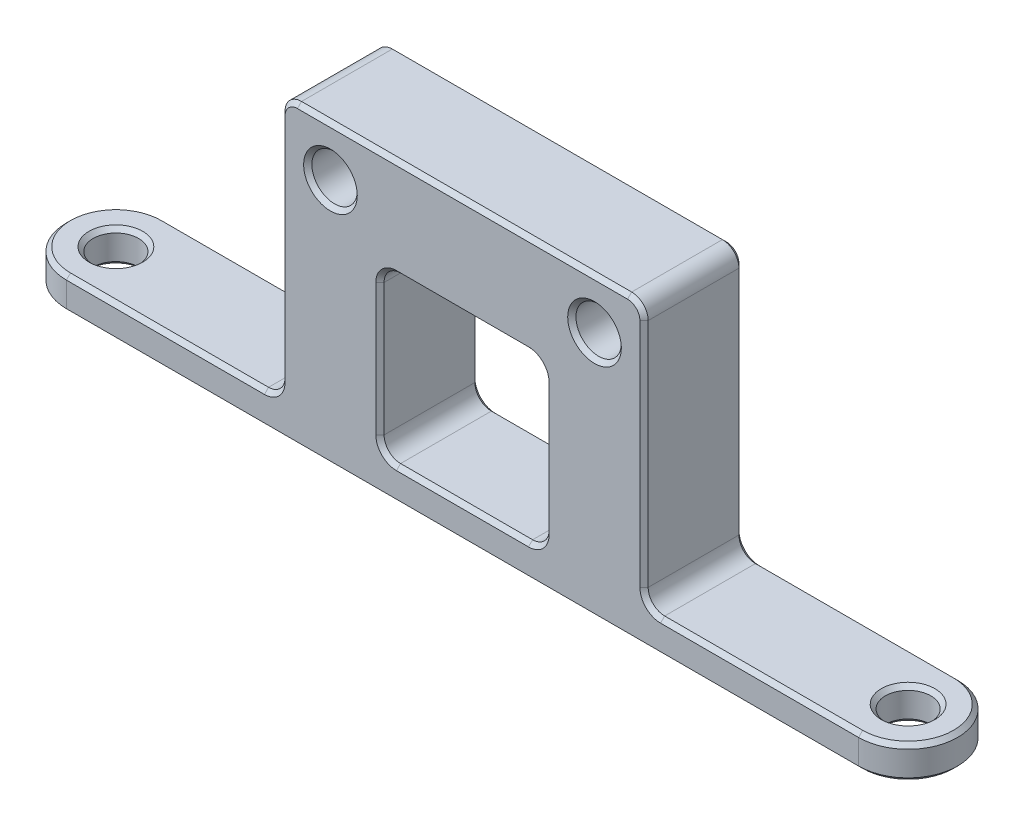
SolidWorks part; units mm, degrees
ref_plane "Front Plane" through (0, 0, 0) normal (0, 0, 1) x (1, 0, 0)
ref_plane "Top Plane" through (0, 0, 0) normal (0, 1, 0) x (1, 0, 0)
ref_plane "Right Plane" through (0, 0, 0) normal (1, 0, 0) x (0, 0, -1)
sketch "Sketch2" plane through (0, 0, 0) normal (0, 1, 0) x (1, 0, 0)
  line L0 (-38.1, 0) -> (38.1, 0) construction
  line L5 (-38.1, 4.7625) -> (38.1, 4.7625)
  line L6 (-38.1, -4.7625) -> (38.1, -4.7625)
  circle A0 centre (-38.1, 0) radius 2.1828
  circle A1 centre (38.1, 0) radius 2.1828
  arc A2 (-38.1, 4.7625) -> (-38.1, -4.7625) centre (-38.1, 0) ccw
  arc A3 (38.1, -4.7625) -> (38.1, 4.7625) centre (38.1, 0) ccw
  point P0 (0, 0)
  point P1 (0, 0)
  dimension "D3" = 4.3656
  dimension "D4" = 4.3656
  dimension "D5" = 4.7625
  dimension "D1" = 38.1
  dimension "D2" = 38.1
extrude "Boss-Extrude1" add sketch "Sketch2" along normal blind 3.175
sketch "Sketch3" plane through (0, 3.175, 0) normal (0, 1, 0) x (1, 0, 0)
  line L0 (38.1, 4.7625) -> (-38.1, 4.7625) construction
  line L1 (-18.4216, -4.7625) -> (18.4216, -4.7625)
  line L2 (-18.4216, -4.7625) -> (-18.4216, 4.7625)
  line L3 (-18.4216, 4.7625) -> (18.4216, 4.7625)
  line L4 (18.4216, -4.7625) -> (18.4216, 4.7625)
  line L5 (-18.4216, -4.7625) -> (18.4216, 4.7625) construction
  line L6 (-18.4216, 4.7625) -> (18.4216, -4.7625) construction
  point P0 (0, 0)
  point P12 (0, 0)
  dimension "D1" = 36.8432
extrude "Boss-Extrude2" add sketch "Sketch3" along normal blind 25.4
sketch "Sketch4" plane through (0, 0, 4.7625) normal (0, 0, 1) x (1, 0, 0)
  line L0 (-18.4216, 28.575) -> (18.4216, 28.575) construction
  line L1 (-38.1, 3.175) -> (-18.4216, 3.175) construction
  line L2 (-18.4216, 28.575) -> (-17.4625, 28.575)
  line L3 (-18.4216, 28.575) -> (-18.4216, 3.175)
  line L4 (-18.4216, 3.175) -> (-17.4625, 3.175)
  line L5 (-17.4625, 28.575) -> (-17.4625, 3.175)
  line L6 (18.4216, 3.175) -> (38.1, 3.175) construction
  line L7 (18.4216, 28.575) -> (17.4625, 28.575)
  line L8 (18.4216, 28.575) -> (18.4216, 3.175)
  line L9 (18.4216, 3.175) -> (17.4625, 3.175)
  line L10 (17.4625, 28.575) -> (17.4625, 3.175)
  line L12 (-7.9375, 3.175) -> (7.9375, 3.175)
  line L13 (-7.9375, 3.175) -> (-7.9375, 19.05)
  line L14 (-7.9375, 19.05) -> (7.9375, 19.05)
  line L15 (7.9375, 3.175) -> (7.9375, 19.05)
  circle A0 centre (-12.7, 23.8125) radius 2.1828
  circle A1 centre (12.7, 23.8125) radius 2.1828
  dimension "D6" = 4.3656
  dimension "D7" = 4.3656
  dimension "D1" = 12.7
  dimension "D2" = 12.7
  dimension "D3" = 4.7625
  dimension "D4" = 4.7625
  dimension "D5" = 4.7625
  dimension "D8" = 4.7625
  dimension "D9" = 4.7625
  dimension "D10" = 4.7625
  dimension "D11" = 4.7625
extrude "Cut-Extrude1" cut sketch "Sketch4" against normal through all both and the other way through all
fillet "Fillet1" radius 1.5875 8 edges at (-17.4625, 28.575, 0) (-17.4625, 3.175, 0) (17.4625, 28.575, 0) (17.4625, 3.175, 0) (-7.9375, 19.05, 0) (7.9375, 19.05, 0) (7.9375, 3.175, 0) (-7.9375, 3.175, 0)
chamfer "Chamfer1" distance 0.3969 angle 45 48 edges at (-14.8828, 23.8125, 4.7625) (-10.5172, 23.8125, -4.7625) (10.5172, 23.8125, 4.7625) (14.8828, 23.8125, -4.7625) (38.1, 3.175, 2.1828) (-38.1, 3.175, 2.1828) (0, 19.05, -4.7625) (-7.4725, 18.585, -4.7625) (7.4725, 18.585, -4.7625) (-7.9375, 11.1125, -4.7625) (7.9375, 11.1125, -4.7625) (-7.4725, 3.64, -4.7625) (7.4725, 3.64, -4.7625) (0, 3.175, -4.7625) (0, 19.05, 4.7625) (7.4725, 18.585, 4.7625) (-7.4725, 18.585, 4.7625) (7.9375, 11.1125, 4.7625) (-7.9375, 11.1125, 4.7625) (7.4725, 3.64, 4.7625) (-7.4725, 3.64, 4.7625) (0, 3.175, 4.7625) (38.1, 0, 2.1828) (-38.1, 0, 2.1828) (0, 0, 4.7625) (42.8625, 0, 0) (0, 0, -4.7625) (-42.8625, 0, 0) (0, 28.575, 4.7625) (16.9975, 28.11, 4.7625) (-16.9975, 28.11, 4.7625) (17.4625, 15.875, 4.7625) (-17.4625, 15.875, 4.7625) (17.9275, 3.64, 4.7625) (-17.9275, 3.64, 4.7625) (28.575, 3.175, 4.7625) (-28.575, 3.175, 4.7625) (42.8625, 3.175, 0) (-42.8625, 3.175, 0) (28.575, 3.175, -4.7625) (-28.575, 3.175, -4.7625) (17.9275, 3.64, -4.7625) (-17.9275, 3.64, -4.7625) (17.4625, 15.875, -4.7625) (-17.4625, 15.875, -4.7625) (16.9975, 28.11, -4.7625) (-16.9975, 28.11, -4.7625) (0, 28.575, -4.7625)
